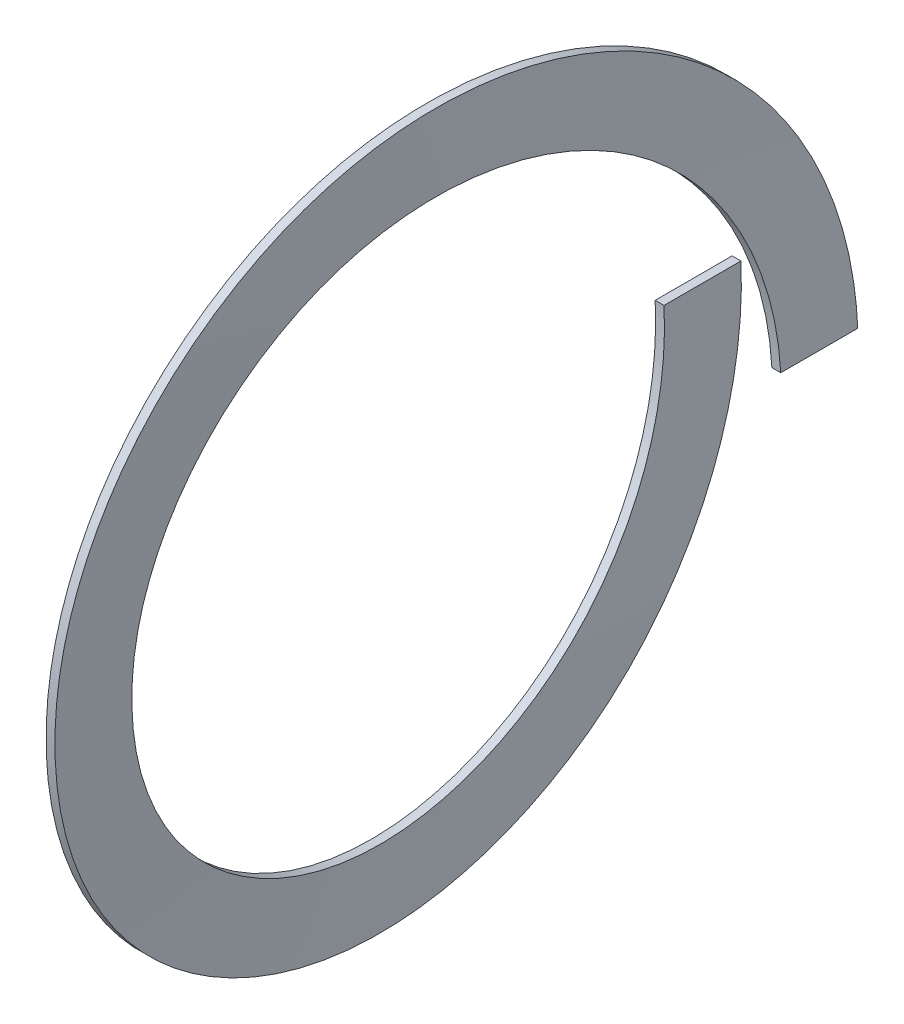
SolidWorks part; units mm, degrees
ref_plane "Plan de face" through (0, 0, 0) normal (0, 0, 1) x (1, 0, 0)
ref_plane "Plan de dessus" through (0, 0, 0) normal (0, 1, 0) x (1, 0, 0)
ref_plane "Plan de droite" through (0, 0, 0) normal (1, 0, 0) x (0, 0, -1)
sketch "Sketch2" plane through (0, 0, 0) normal (1, 0, 0) x (0, 0, -1)
  circle A0 centre (0, 0) radius 2
curve "Helix/Spiral1" pitch 0.7 height 0.7 radius 2 left hand yes centre (0, 0, 0) axis (1, 0, 0) start towards (0, 0, -1)
sketch "Sketch4" plane through (0, 0, 0) normal (0, 1, 0) x (1, 0, 0)
  line L1 (0.0265, 1.7692) -> (-0.0265, 1.7692)
  line L2 (0.0265, 1.7692) -> (0.0265, 2.2308)
  line L3 (0.0265, 2.2308) -> (-0.0265, 2.2308)
  line L4 (-0.0265, 1.7692) -> (-0.0265, 2.2308)
  line L5 (0.0265, 1.7692) -> (-0.0265, 2.2308) construction
  line L6 (0.0265, 2.2308) -> (-0.0265, 1.7692) construction
  spline S0 degree 3 poles (0, 2) (0.0145, 2) (0.0438, 1.8959) (0.0875, 1.451) (0.1313, 0.7853) (0.175, 0) (0.2188, -0.7853) (0.2625, -1.451) (0.3063, -1.8959) (0.35, -2.0521) (0.3937, -1.8959) (0.4375, -1.451) (0.4812, -0.7853) (0.525, 0) (0.5687, 0.7853) (0.6125, 1.451) (0.6562, 1.8959) (0.6855, 2) (0.7, 2) knots 0 0 0 0 0.0625 0.125 0.1875 0.25 0.3125 0.375 0.4375 0.5 0.5625 0.625 0.6875 0.75 0.8125 0.875 0.9375 1 1 1 1 construction
  point P0 (0, 2)
sweep "Sweep1" add profiles "Sketch4" path "Helix/Spiral1"
